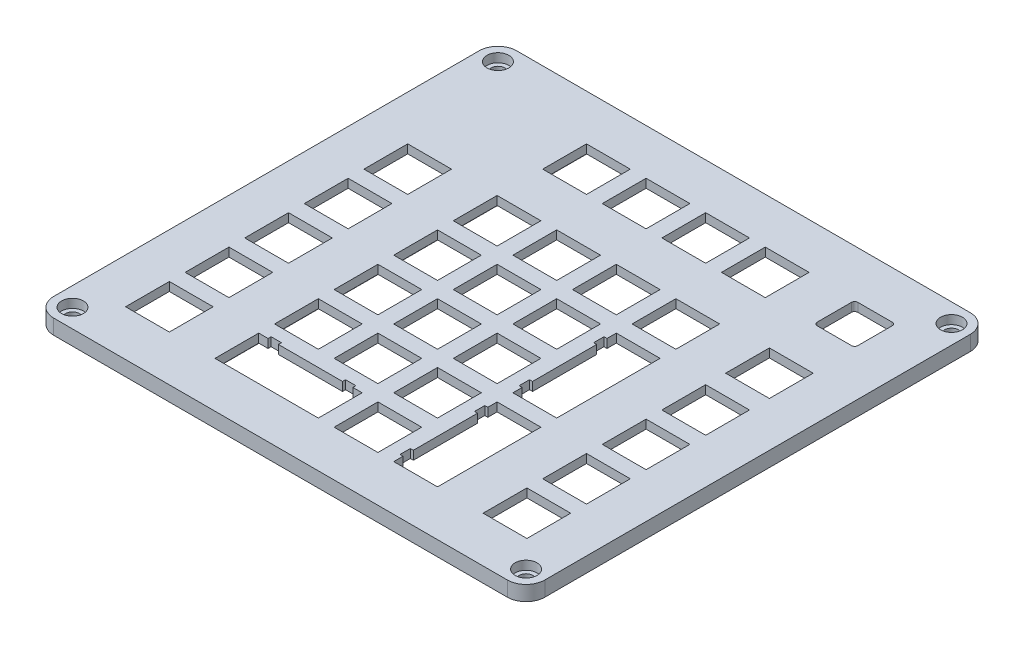
SolidWorks part; units mm, degrees
material "ABS PC"
ref_plane "Front" through (0, 0, 0) normal (0, 0, 1) x (1, 0, 0)
ref_plane "Top" through (0, 0, 0) normal (0, 1, 0) x (1, 0, 0)
ref_plane "Right" through (0, 0, 0) normal (1, 0, 0) x (0, 0, -1)
other "Bounding Box"
ref_plane "Default Plane" through (-37.2876, 0, 53.2522) normal (-0.1736, 0, -0.9848) x (-0.9848, 0, 0.1736)
sketch "Sketch1" plane through (0, 0, 0) normal (0, 1, 0) x (1, 0, 0)
  line L0 (78.5946, 148.4241) -> (78.5951, 0.4241) construction
  line L1 (0.0951, 74.4246) -> (157.0951, 74.4241) construction
  line L2 (76.0691, 29.038) -> (43.0195, 15.0385) construction
  line L3 (43.0195, 29.038) -> (76.0691, 15.0385) construction
  line L4 (135.7441, 106.5548) -> (135.7441, 137.3637) construction
  line L5 (114.1691, 126.8136) -> (153.3059, 126.8136) construction
  line L7 (129.2441, 133.3136) -> (142.2441, 133.3136)
  line L8 (129.2441, 133.3136) -> (129.2441, 120.3136)
  line L9 (129.2441, 120.3136) -> (142.2441, 120.3136)
  line L10 (142.2441, 133.3136) -> (142.2441, 120.3136)
  line L11 (129.2441, 133.3136) -> (142.2441, 120.3136) construction
  line L12 (129.2441, 120.3136) -> (142.2441, 133.3136) construction
  line L20 (157.0951, 142.4241) -> (157.0951, 6.4241)
  line L41 (151.0951, 0.4241) -> (6.0951, 0.4241)
  line L62 (0.0951, 6.424) -> (0.0951, 142.4251)
  line L83 (6.0941, 148.4241) -> (151.0951, 148.4241)
  line L84 (76.0691, 15.0385) -> (76.0691, 29.038)
  line L85 (76.0691, 29.038) -> (73.0938, 29.038)
  line L86 (73.0938, 29.038) -> (73.0938, 30.0081)
  line L87 (73.0938, 30.0081) -> (69.795, 30.0081)
  line L88 (69.795, 30.0081) -> (69.795, 29.038)
  line L89 (69.795, 29.038) -> (49.2936, 29.038)
  line L90 (49.2936, 29.038) -> (49.2936, 30.0081)
  line L91 (49.2936, 30.0081) -> (45.9948, 30.0081)
  line L92 (45.9948, 30.0081) -> (45.9948, 29.038)
  line L93 (45.9948, 29.038) -> (43.0195, 29.038)
  line L94 (43.0195, 29.038) -> (43.0195, 15.0385)
  line L95 (43.0195, 15.0385) -> (76.0691, 15.0385)
  line L96 (128.7441, 29.038) -> (142.7441, 29.038)
  line L97 (142.7441, 29.038) -> (142.7441, 15.0385)
  line L98 (142.7441, 15.0385) -> (128.7441, 15.0385)
  line L99 (128.7441, 15.0385) -> (128.7441, 29.038)
  line L100 (100.1691, 48.0882) -> (100.1691, 45.1129)
  line L101 (100.1691, 45.1129) -> (99.1995, 45.1129)
  line L102 (99.1995, 45.1129) -> (99.1995, 41.8123)
  line L103 (99.1995, 41.8123) -> (100.1691, 41.8123)
  line L104 (100.1691, 41.8123) -> (100.1691, 21.3128)
  line L105 (100.1691, 21.3128) -> (99.1995, 21.3128)
  line L106 (99.1995, 21.3128) -> (99.1995, 18.0123)
  line L107 (99.1995, 18.0123) -> (100.1691, 18.0123)
  line L108 (100.1691, 18.0123) -> (100.1691, 15.0385)
  line L109 (100.1691, 15.0385) -> (114.1691, 15.0385)
  line L110 (114.1691, 15.0385) -> (114.1691, 48.0882)
  line L111 (114.1691, 48.0882) -> (100.1691, 48.0882)
  line L112 (81.1195, 29.038) -> (95.1192, 29.038)
  line L113 (95.1192, 29.038) -> (95.1192, 15.0385)
  line L114 (95.1192, 15.0385) -> (81.1195, 15.0385)
  line L115 (81.1195, 15.0385) -> (81.1195, 29.038)
  line L116 (14.4432, 29.038) -> (28.4441, 29.038)
  line L117 (28.4441, 29.038) -> (28.4441, 15.0385)
  line L118 (28.4441, 15.0385) -> (14.4432, 15.0385)
  line L119 (14.4432, 15.0385) -> (14.4432, 29.038)
  line L120 (128.7441, 48.0882) -> (142.7441, 48.0882)
  line L121 (142.7441, 48.0882) -> (142.7441, 34.0885)
  line L122 (142.7441, 34.0885) -> (128.7441, 34.0885)
  line L123 (128.7441, 34.0885) -> (128.7441, 48.0882)
  line L124 (81.1195, 48.0882) -> (95.1192, 48.0882)
  line L125 (95.1192, 48.0882) -> (95.1192, 34.0885)
  line L126 (95.1192, 34.0885) -> (81.1195, 34.0885)
  line L127 (81.1195, 34.0885) -> (81.1195, 48.0882)
  line L128 (62.0695, 48.0882) -> (76.0691, 48.0882)
  line L129 (76.0691, 48.0882) -> (76.0691, 34.0885)
  line L130 (76.0691, 34.0885) -> (62.0695, 34.0885)
  line L131 (62.0695, 34.0885) -> (62.0695, 48.0882)
  line L132 (43.0195, 48.0882) -> (57.0191, 48.0882)
  line L133 (57.0191, 48.0882) -> (57.0191, 34.0885)
  line L134 (57.0191, 34.0885) -> (43.0195, 34.0885)
  line L135 (43.0195, 34.0885) -> (43.0195, 48.0882)
  line L136 (14.4432, 48.0882) -> (28.4441, 48.0882)
  line L137 (28.4441, 48.0882) -> (28.4441, 34.0885)
  line L138 (28.4441, 34.0885) -> (14.4432, 34.0885)
  line L139 (14.4432, 34.0885) -> (14.4432, 48.0882)
  line L140 (128.7441, 67.1382) -> (142.7441, 67.1382)
  line L141 (142.7441, 67.1382) -> (142.7441, 53.1386)
  line L142 (142.7441, 53.1386) -> (128.7441, 53.1386)
  line L143 (128.7441, 53.1386) -> (128.7441, 67.1382)
  line L144 (100.1691, 86.1882) -> (100.1691, 83.2129)
  line L145 (100.1691, 83.2129) -> (99.1995, 83.2129)
  line L146 (99.1995, 83.2129) -> (99.1995, 79.9123)
  line L147 (99.1995, 79.9123) -> (100.1691, 79.9123)
  line L148 (100.1691, 79.9123) -> (100.1691, 59.4127)
  line L149 (100.1691, 59.4127) -> (99.1995, 59.4127)
  line L150 (99.1995, 59.4127) -> (99.1995, 56.1125)
  line L151 (99.1995, 56.1125) -> (100.1691, 56.1125)
  line L152 (100.1691, 56.1125) -> (100.1691, 53.1386)
  line L153 (100.1691, 53.1386) -> (114.1691, 53.1386)
  line L154 (114.1691, 53.1386) -> (114.1691, 86.1882)
  line L155 (114.1691, 86.1882) -> (100.1691, 86.1882)
  line L156 (81.1195, 67.1382) -> (95.1192, 67.1382)
  line L157 (95.1192, 67.1382) -> (95.1192, 53.1386)
  line L158 (95.1192, 53.1386) -> (81.1195, 53.1386)
  line L159 (81.1195, 53.1386) -> (81.1195, 67.1382)
  line L160 (62.0695, 67.1382) -> (76.0691, 67.1382)
  line L161 (76.0691, 67.1382) -> (76.0691, 53.1386)
  line L162 (76.0691, 53.1386) -> (62.0695, 53.1386)
  line L163 (62.0695, 53.1386) -> (62.0695, 67.1382)
  line L164 (43.0195, 67.1382) -> (57.0191, 67.1382)
  line L165 (57.0191, 67.1382) -> (57.0191, 53.1386)
  line L166 (57.0191, 53.1386) -> (43.0195, 53.1386)
  line L167 (43.0195, 53.1386) -> (43.0195, 67.1382)
  line L168 (14.4432, 67.1382) -> (28.4441, 67.1382)
  line L169 (28.4441, 67.1382) -> (28.4441, 53.1386)
  line L170 (28.4441, 53.1386) -> (14.4432, 53.1386)
  line L171 (14.4432, 53.1386) -> (14.4432, 67.1382)
  line L172 (128.7441, 86.1882) -> (142.7441, 86.1882)
  line L173 (142.7441, 86.1882) -> (142.7441, 72.1886)
  line L174 (142.7441, 72.1886) -> (128.7441, 72.1886)
  line L175 (128.7441, 72.1886) -> (128.7441, 86.1882)
  line L176 (81.1195, 86.1882) -> (95.1192, 86.1882)
  line L177 (95.1192, 86.1882) -> (95.1192, 72.1886)
  line L178 (95.1192, 72.1886) -> (81.1195, 72.1886)
  line L179 (81.1195, 72.1886) -> (81.1195, 86.1882)
  line L180 (62.0695, 86.1882) -> (76.0691, 86.1882)
  line L181 (76.0691, 86.1882) -> (76.0691, 72.1886)
  line L182 (76.0691, 72.1886) -> (62.0695, 72.1886)
  line L183 (62.0695, 72.1886) -> (62.0695, 86.1882)
  line L184 (43.0195, 86.1882) -> (57.0191, 86.1882)
  line L185 (57.0191, 86.1882) -> (57.0191, 72.1886)
  line L186 (57.0191, 72.1886) -> (43.0195, 72.1886)
  line L187 (43.0195, 72.1886) -> (43.0195, 86.1882)
  line L188 (14.4432, 86.1882) -> (28.4441, 86.1882)
  line L189 (28.4441, 86.1882) -> (28.4441, 72.1886)
  line L190 (28.4441, 72.1886) -> (14.4432, 72.1886)
  line L191 (14.4432, 72.1886) -> (14.4432, 86.1882)
  line L192 (128.7441, 106.5548) -> (142.7441, 106.5548)
  line L193 (142.7441, 106.5548) -> (142.7441, 92.5554)
  line L194 (142.7441, 92.5554) -> (128.7441, 92.5554)
  line L195 (128.7441, 92.5554) -> (128.7441, 106.5548)
  line L196 (100.1691, 105.2381) -> (114.1691, 105.2381)
  line L197 (114.1691, 105.2381) -> (114.1691, 91.2386)
  line L198 (114.1691, 91.2386) -> (100.1691, 91.2386)
  line L199 (100.1691, 91.2386) -> (100.1691, 105.2381)
  line L200 (81.1195, 105.2381) -> (95.1192, 105.2381)
  line L201 (95.1192, 105.2381) -> (95.1192, 91.2386)
  line L202 (95.1192, 91.2386) -> (81.1195, 91.2386)
  line L203 (81.1195, 91.2386) -> (81.1195, 105.2381)
  line L204 (62.0695, 105.2381) -> (76.0691, 105.2381)
  line L205 (76.0691, 105.2381) -> (76.0691, 91.2386)
  line L206 (76.0691, 91.2386) -> (62.0695, 91.2386)
  line L207 (62.0695, 91.2386) -> (62.0695, 105.2381)
  line L208 (43.0195, 105.2381) -> (57.0191, 105.2381)
  line L209 (57.0191, 105.2381) -> (57.0191, 91.2386)
  line L210 (57.0191, 91.2386) -> (43.0195, 91.2386)
  line L211 (43.0195, 91.2386) -> (43.0195, 105.2381)
  line L212 (14.4432, 105.2381) -> (28.4441, 105.2381)
  line L213 (28.4441, 105.2381) -> (28.4441, 91.2386)
  line L214 (28.4441, 91.2386) -> (14.4432, 91.2386)
  line L215 (14.4432, 91.2386) -> (14.4432, 105.2381)
  line L216 (100.1691, 133.8131) -> (114.1691, 133.8131)
  line L217 (114.1691, 133.8131) -> (114.1691, 119.8141)
  line L218 (114.1691, 119.8141) -> (100.1691, 119.8141)
  line L219 (100.1691, 119.8141) -> (100.1691, 133.8131)
  line L220 (81.1195, 133.8131) -> (95.1192, 133.8131)
  line L221 (95.1192, 133.8131) -> (95.1192, 119.8141)
  line L222 (95.1192, 119.8141) -> (81.1195, 119.8141)
  line L223 (81.1195, 119.8141) -> (81.1195, 133.8131)
  line L224 (62.0695, 133.8131) -> (76.0691, 133.8131)
  line L225 (76.0691, 133.8131) -> (76.0691, 119.8141)
  line L226 (76.0691, 119.8141) -> (62.0695, 119.8141)
  line L227 (62.0695, 119.8141) -> (62.0695, 133.8131)
  line L228 (43.0195, 133.8131) -> (57.0191, 133.8131)
  line L229 (57.0191, 133.8131) -> (57.0191, 119.8141)
  line L230 (57.0191, 119.8141) -> (43.0195, 119.8141)
  line L231 (43.0195, 119.8141) -> (43.0195, 133.8131)
  arc A0 (151.0951, 0.4241) -> (157.0951, 6.4241) centre (151.0951, 6.4241) ccw
  arc A1 (6.0951, 0.4241) -> (0.0951, 6.424) centre (6.0951, 6.424) cw
  arc A2 (0.0951, 142.4251) -> (6.0941, 148.4241) centre (6.0941, 142.4251) cw
  arc A3 (151.0951, 148.4241) -> (157.0951, 142.4241) centre (151.0951, 142.4241) cw
  circle A4 centre (6.0951, 142.4241) radius 2.15
  circle A5 centre (151.0941, 142.4246) radius 2.15
  circle A6 centre (151.0937, 6.4236) radius 2.15
  circle A7 centre (6.0947, 6.425) radius 2.15
  point P11 (151.0951, 142.4255)
  point P22 (135.7441, 126.8136)
  point P25 (135.7441, 126.8136)
  dimension "D1" = 157
  dimension "D3" = 6
  dimension "D5" = 4.3
  dimension "D2" = 148
  dimension "D4" = 6
  dimension "D6" = 13
  dimension "D7" = 13
extrude "Boss-Extrude1" add sketch "Sketch1" along normal blind 4.78
sketch "Sketch2" plane through (0, 0, 0) normal (0, -1, 0) x (1, 0, 0)
  line L0 (10.0951, -10.4241) -> (10.0951, -138.4241)
  line L1 (10.0951, -138.4241) -> (147.0951, -138.4241)
  line L2 (147.0951, -138.4241) -> (147.0951, -10.4241)
  line L3 (147.0951, -10.4241) -> (10.0951, -10.4241)
  line L4 (157.0951, -142.4241) -> (157.0951, -6.4241)
  line L5 (151.0951, -0.4241) -> (6.0951, -0.4241)
  line L6 (0.0951, -6.424) -> (0.0951, -142.4251)
  line L7 (6.0941, -148.4241) -> (151.0951, -148.4241)
  line L8 (157.0951, -142.4241) -> (157.0951, -6.4241)
  line L9 (151.0951, -0.4241) -> (6.0951, -0.4241)
  line L10 (0.0951, -6.424) -> (0.0951, -142.4251)
  line L11 (6.0941, -148.4241) -> (151.0951, -148.4241)
  arc A4 (151.0951, -148.4241) -> (157.0951, -142.4241) centre (151.0951, -142.4241) ccw
  arc A5 (157.0951, -6.4241) -> (151.0951, -0.4241) centre (151.0951, -6.4241) ccw
  arc A6 (6.0951, -0.4241) -> (0.0951, -6.424) centre (6.0951, -6.424) ccw
  arc A7 (0.0951, -142.4251) -> (6.0941, -148.4241) centre (6.0941, -142.4251) ccw
  arc A8 (151.0951, -148.4241) -> (157.0951, -142.4241) centre (151.0951, -142.4241) ccw
  arc A9 (157.0951, -6.4241) -> (151.0951, -0.4241) centre (151.0951, -6.4241) ccw
  arc A10 (6.0951, -0.4241) -> (0.0951, -6.424) centre (6.0951, -6.424) ccw
  arc A11 (0.0951, -142.4251) -> (6.0941, -148.4241) centre (6.0941, -142.4251) ccw
  dimension "D2" = 10
  dimension "D3" = 10
  dimension "D4" = 10
  dimension "D5" = 10
  dimension "D1" = 0
extrude "Cut-Extrude1" cut sketch "Sketch2" against normal blind 2 contours L2 L3 L0 L1 region at (78.5951, 0, -74.4241)
sketch "Sketch4" plane through (0, 0, 0) normal (0, -1, 0) x (1, 0, 0)
  line L0 (132.0951, -138.4241) -> (132.0951, -145.4241)
  line L1 (10.0951, -138.4241) -> (147.0951, -138.4241) construction
  line L2 (132.0951, -145.4241) -> (117.0951, -145.4241)
  line L3 (117.0951, -145.4241) -> (117.0951, -138.4241)
  line L4 (117.0951, -138.4241) -> (132.0951, -138.4241)
  line L5 (151.0951, -148.4241) -> (6.0941, -148.4241) construction
  line L6 (147.0951, -138.4241) -> (147.0951, -10.4241) construction
  dimension "D1" = 3
  dimension "D2" = 15
  dimension "D3" = 15
extrude "Cut-Extrude2" cut sketch "Sketch4" against normal blind 2
sketch "Sketch5" plane through (0, 0, 0) normal (0, -1, 0) x (1, 0, 0)
  line L0 (15.0951, -145.9241) -> (15.0951, -138.4241)
  line L2 (10.0951, -138.4241) -> (117.0951, -138.4241) construction
  line L3 (15.0951, -138.4241) -> (35.0951, -138.4241)
  line L4 (10.0951, -138.4241) -> (117.0951, -138.4241) construction
  line L5 (35.0951, -138.4241) -> (35.0951, -145.9241)
  line L6 (35.0951, -145.9241) -> (15.0951, -145.9241)
  line L7 (0.0951, -142.4251) -> (0.0951, -6.424) construction
  line L8 (151.0951, -148.4241) -> (6.0941, -148.4241) construction
  point P12 (25.0951, -145.9241)
  dimension "D1" = 25
  dimension "D2" = 20
  dimension "D3" = 2.5
extrude "Cut-Extrude3" cut sketch "Sketch5" against normal blind 2
sketch "Sketch6" plane through (0, 4.78, 0) normal (0, 1, 0) x (1, 0, 0)
  circle A0 centre (6.0951, 142.4241) radius 3.5
  circle A1 centre (151.0941, 142.4246) radius 3.5
  circle A2 centre (151.0937, 6.4236) radius 3.5
  circle A3 centre (6.0947, 6.425) radius 3.5
  dimension "D1" = 7
extrude "Cut-Extrude4" cut sketch "Sketch6" against normal blind 2.8
fillet "Fillet1" radius 1 4 edges at (142.2441, 3.39, -120.3136) (129.2441, 3.39, -120.3136) (142.2441, 3.39, -133.3136) (129.2441, 3.39, -133.3136)
sketch "Sketch7" plane through (0, 2, 0) normal (0, -1, 0) x (1, 0, 0)
  line L0 (35.0951, -138.4241) -> (35.0951, -10.4241)
  line L1 (147.0951, -10.4241) -> (10.0951, -10.4241) construction
  line L2 (35.0951, -10.4241) -> (41.0951, -10.4241)
  line L3 (147.0951, -10.4241) -> (10.0951, -10.4241) construction
  line L4 (41.0951, -10.4241) -> (41.0951, -138.4241)
  line L5 (35.0951, -138.4241) -> (117.0951, -138.4241) construction
  line L6 (41.0951, -138.4241) -> (35.0951, -138.4241)
  dimension "D1" = 6
extrude "Boss-Extrude2" add sketch "Sketch7" along normal blind 2
sketch "Sketch8" plane through (0, 2, 0) normal (0, -1, 0) x (1, 0, 0)
  line L0 (41.0951, -116.2381) -> (116.0951, -116.2381)
  line L1 (41.0951, -138.4241) -> (41.0951, -10.4241) construction
  line L2 (116.0951, -116.2381) -> (116.0951, -109.2381)
  line L3 (116.0951, -109.2381) -> (41.0951, -109.2381)
  line L4 (41.0951, -138.4241) -> (41.0951, -10.4241) construction
  line L5 (41.0951, -109.2381) -> (41.0951, -116.2381)
  line L6 (43.0195, -105.2381) -> (57.0191, -105.2381) construction
  point P10 (41.0951, -112.7381)
  dimension "D1" = 75
  dimension "D2" = 7
  dimension "D3" = 7.5
extrude "Boss-Extrude3" add sketch "Sketch8" along normal blind 2
sketch "Sketch9" plane through (0, 2, 0) normal (0, -1, 0) x (1, 0, 0)
  line L0 (120.7441, -10.4241) -> (120.7441, -105.4241)
  line L1 (147.0951, -10.4241) -> (41.0951, -10.4241) construction
  line L2 (120.7441, -105.4241) -> (126.7441, -105.4241)
  line L3 (126.7441, -105.4241) -> (126.7441, -10.4241)
  line L4 (147.0951, -10.4241) -> (41.0951, -10.4241) construction
  line L5 (126.7441, -10.4241) -> (120.7441, -10.4241)
  line L6 (128.7441, -15.0385) -> (128.7441, -29.038) construction
  point P10 (123.7441, -10.4241)
  dimension "D1" = 5
  dimension "D2" = 6
  dimension "D3" = 95
extrude "Boss-Extrude4" add sketch "Sketch9" along normal blind 2
sketch "Sketch10" plane through (0, 2, 0) normal (0, -1, 0) x (1, 0, 0)
  line L0 (147.0951, -116.2381) -> (132.0951, -116.2381)
  line L1 (147.0951, -138.4241) -> (147.0951, -10.4241) construction
  line L2 (132.0951, -116.2381) -> (132.0951, -109.2381)
  line L3 (132.0951, -109.2381) -> (147.0951, -109.2381)
  line L4 (147.0951, -138.4241) -> (147.0951, -10.4241) construction
  line L5 (147.0951, -109.2381) -> (147.0951, -116.2381)
  line L6 (116.0951, -109.2381) -> (41.0951, -109.2381) construction
  line L7 (41.0951, -116.2381) -> (116.0951, -116.2381) construction
  dimension "D1" = 15
extrude "Boss-Extrude5" add sketch "Sketch10" along normal blind 2
fillet "Fillet2" radius 2.5 26 edges at (116.0951, 1, -109.2381) (116.0951, 1, -116.2381) (120.7441, 1, -10.4241) (120.7441, 1, -105.4241) (126.7441, 1, -105.4241) (126.7441, 1, -10.4241) (147.0951, 1, -10.4241) (147.0951, 1, -138.4241) (132.0951, 1, -138.4241) (132.0951, 1, -145.4241) (117.0951, 1, -145.4241) (117.0951, 1, -138.4241) (41.0951, 1, -138.4241) (41.0951, 1, -116.2381) (41.0951, 1, -109.2381) (41.0951, 1, -10.4241) (10.0951, 1, -10.4241) (10.0951, 1, -138.4241) (15.0951, 1, -138.4241) (15.0951, 1, -145.9241) (35.0951, 1, -145.9241) (35.0951, 1, -10.4241) (147.0951, 1, -109.2381) (132.0951, 1, -109.2381) (132.0951, 1, -116.2381) (147.0951, 1, -116.2381)
